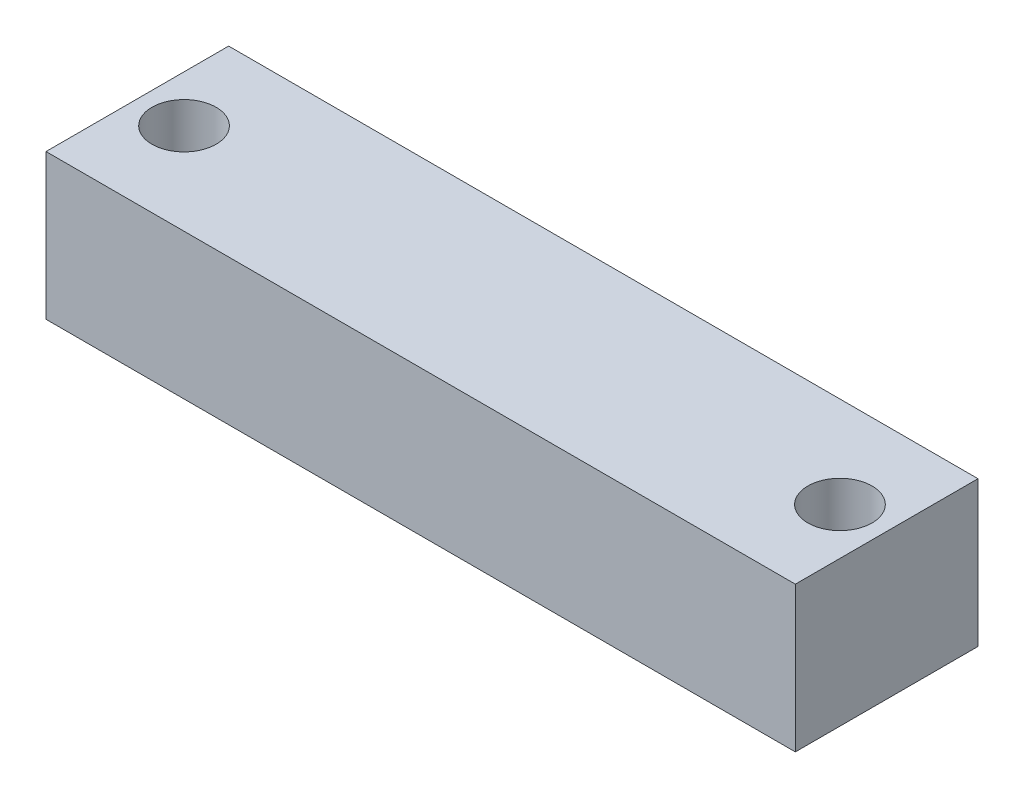
SolidWorks part; units mm, degrees
ref_plane "Front Plane" through (0, 0, 0) normal (0, 0, 1) x (1, 0, 0)
ref_plane "Top Plane" through (0, 0, 0) normal (0, 1, 0) x (1, 0, 0)
ref_plane "Right Plane" through (0, 0, 0) normal (1, 0, 0) x (0, 0, -1)
sketch "Sketch1" plane through (0, 0, 0) normal (0, 1, 0) x (1, 0, 0)
  line L1 (-45.125, -11) -> (45.125, -11)
  line L2 (-45.125, -11) -> (-45.125, 11)
  line L3 (-45.125, 11) -> (45.125, 11)
  line L4 (45.125, -11) -> (45.125, 11)
  line L5 (-45.125, -11) -> (45.125, 11) construction
  line L6 (-45.125, 11) -> (45.125, -11) construction
  point P0 (0, 0)
  dimension "D1" = 90.25
  dimension "D2" = 22
extrude "Boss-Extrude1" add sketch "Sketch1" along normal blind 17.5
sketch "Sketch2" plane through (0, 17.5, 0) normal (0, 1, 0) x (1, 0, 0)
  line L0 (0, 11) -> (0, -11) construction
  line L1 (45.125, 11) -> (-45.125, 11) construction
  line L2 (-45.125, -11) -> (45.125, -11) construction
  line L3 (-45.125, 0) -> (45.125, 0) construction
  line L4 (-45.125, 11) -> (-45.125, -11) construction
  line L5 (45.125, -11) -> (45.125, 11) construction
  circle A0 centre (-39.5, 0) radius 1.5
  circle A1 centre (39.5, 0) radius 1.5
  dimension "D2" = 3
  dimension "D1" = 79
extrude "Cut-Extrude1" cut sketch "Sketch2" against normal through all and the other way through all
sketch "Sketch3" plane through (0, 17.5, 0) normal (0, 1, 0) x (1, 0, 0)
  line L1 (-43.365, 11) -> (-43.365, -11)
  line L2 (-45.125, 11) -> (-45.125, -11) construction
  line L3 (45.125, 11) -> (-45.125, 11) construction
  line L4 (-45.125, -11) -> (45.125, -11) construction
  circle A0 centre (-39.5, 0) radius 3.865
  circle A1 centre (39.5, 0) radius 3.865
  circle M2 centre (-39.5, 0) radius 1.5
  circle M3 centre (39.5, 0) radius 1.5
  dimension "D1" = 1.76
extrude "Cut-Extrude2" cut sketch "Sketch3" against normal blind 10 contours A0 M2 | A1 M3 region at (-39.5, 17.5, 3.7557) region at (35.7443, 17.5, 0)
